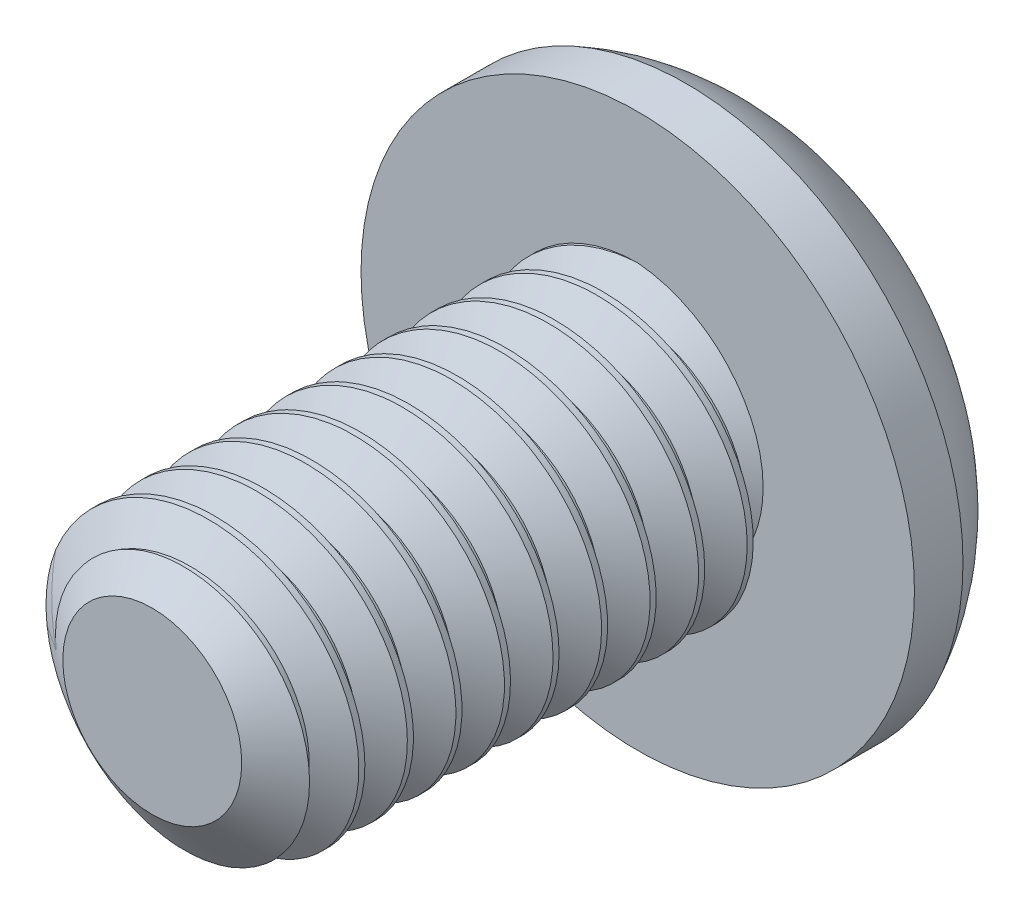
SolidWorks part; units mm, degrees
ref_plane "Front Plane" through (0, 0, 0) normal (0, 0, 1) x (1, 0, 0)
ref_plane "Top Plane" through (0, 0, 0) normal (0, 1, 0) x (1, 0, 0)
ref_plane "Right Plane" through (0, 0, 0) normal (1, 0, 0) x (0, 0, -1)
sketch "Sketch1" plane through (0, 0, 0) normal (0, 0, 1) x (1, 0, 0)
  circle A0 centre (0, 0) radius 1.5
  dimension "OD" = 3
extrude "Extrude1" add sketch "Sketch1" against normal blind 5
sketch "Sketch2" plane through (0, 0, 0) normal (0, 0, 1) x (1, 0, 0)
  circle A0 centre (0, 0) radius 1.5 construction
  circle A1 centre (0, 0) radius 1.5
curve "Helix/Spiral1" pitch 0.5 height 5.5 radius 1.5 centre (0, 0, 0) axis (0, 0, -1) start towards (0, 1, 0) parameters "pitch"=0.5
sketch "Sketch3" plane through (0, 0, 0) normal (1, 0, 0) x (0, 0, -1)
  line L0 (-0.4375, 1.5) -> (-0.25, 1.1752)
  line L1 (-0.25, 1.1752) -> (-0.1875, 1.1752)
  line L2 (-0.1875, 1.1752) -> (0, 1.5)
  line L3 (-0.4375, 1.5) -> (0, 1.5)
  line L4 (-0.2187, 1.5) -> (-0.2187, 1.1752) construction
  line L5 (-0.3437, 1.3376) -> (-0.0937, 1.3376) construction
  line L6 (0, 1.5) -> (0, -1.5) construction
  dimension "D1" = 0.0625
  dimension "D2" = 0.25
  dimension "D3" = 60
sweep "Cut-Sweep1" cut profiles "Sketch3" path "Helix/Spiral1"
sketch "Sketch4" plane through (0, 0, 0) normal (1, 0, 0) x (0, 0, -1)
  line L0 (0.4053, 1.5) -> (0, 0.9212)
  line L1 (0, 0.9212) -> (0, 1.5)
  line L2 (0.4053, 1.5) -> (0, 1.5)
  line L3 (-0.4375, 1.5) -> (0, 1.5) construction
  line L4 (0, 0) -> (7.0209, 0) construction
  dimension "D1" = 55
  dimension "D2" = 0.254
revolve "Cut-Revolve1" cut sketch "Sketch4" angle 360 about L4
sketch "Sketch5" plane through (0, 0, 0) normal (1, 0, 0) x (0, 0, -1)
  line L0 (5, -1.1822) -> (5, 1.0703) construction
  line L1 (5, 1.627) -> (28.1202, 1.627)
  line L2 (5, 1.627) -> (5, 0)
  line L3 (5, 0) -> (28, 0)
  line L4 (28, 1.2968) -> (28, 0)
  line L5 (28.1202, 1.627) -> (28, 1.2968)
  line L6 (0, 0) -> (9.9695, 0) construction
  point P3 (28, 1.627)
  point P10 (28, 1.627)
  dimension "D1" = 0.3302
  dimension "Thread min" = 28
  dimension "D2" = 0.127
  dimension "D3" = 20
revolve "partially thread" [suppressed] add sketch "Sketch5" angle 360 about L6
sketch "Sketch6" plane through (0, 0, -5) normal (0, 0, -1) x (-1, 0, 0)
  circle A0 centre (0, 0) radius 2.85
  dimension "head dia" = 5.7
extrude "Extrude2" add sketch "Sketch6" along normal blind 1.65
sketch "Sketch10" plane through (0, 0, 0) normal (1, 0, 0) x (0, 0, -1)
  line L0 (6.65, -2.85) -> (6.65, 2.85) construction
  line L1 (0, 0) -> (15.9584, 0) construction
  line L2 (6.65, 2.85) -> (5, 2.85) construction
  line L3 (5, 2.85) -> (5, -2.85) construction
  line L4 (5.5, 2.85) -> (5.5, 3.35)
  line L5 (5.5, 3.35) -> (7.15, 3.35)
  line L6 (7.15, 3.35) -> (7.15, 1)
  line L7 (6.65, 1) -> (7.15, 1)
  arc A0 (6.65, 1) -> (5.5, 2.85) centre (4.587, 1) ccw
  dimension "D1" = 2
  dimension "D2" = 0.5
  dimension "D3" = 0.5
revolve "Cut-Revolve2" cut sketch "Sketch10" angle 360 about L1
ref_plane "Plane1" through (0, 0, -6.65) normal (0, 0, 1) x (1, 0, 0)
sketch "Sketch7" plane through (0, 0, -6.65) normal (0, 0, -1) x (-1, 0, 0)
  line L1 (0, 1.1547) -> (-1, 0.5774)
  line L2 (-1, 0.5774) -> (-1, -0.5774)
  line L3 (-1, -0.5774) -> (0, -1.1547)
  line L4 (0, -1.1547) -> (1, -0.5774)
  line L5 (1, -0.5774) -> (1, 0.5774)
  line L6 (1, 0.5774) -> (0, 1.1547)
  circle A0 centre (0, 0) radius 1 construction
  dimension "hex dia" = 2
extrude "Cut-Extrude1" cut sketch "Sketch7" against normal blind 1.5
sketch "Sketch8" plane through (0, 0, -6.65) normal (0, 0, 1) x (1, 0, 0)
  circle A0 centre (0, 0) radius 1.1547
extrude "Cut-Extrude2" cut sketch "Sketch8" along normal through all draft 45
sketch "Sketch9" plane through (0, 0, 0) normal (1, 0, 0) x (0, 0, -1)
  line L0 (0, 1.5) -> (0, -1.5) construction
  line L1 (2.75, 1.5) -> (2.75, -1.5) construction
  dimension "D1" = 2.75
  dimension "D4" = 0.635
  dimension "D5" = 0.3302
equation "\"D3@Helix/Spiral1\" = \"screw length@Extrude1\"+\"pitch@Helix/Spiral1\""
equation "\"D1@Sketch3\" = \"pitch@Helix/Spiral1\"*.125"
equation "\"D2@Sketch3\" = \"pitch@Helix/Spiral1\"*.5"
equation "\"D1@Cut-Extrude1\" = \"hex dia@Sketch7\"*.75"
equation "\"D1@Sketch9\" = \"pitch@Helix/Spiral1\"*5.5"
equation "\"D1@Sketch10\" = \"hex dia@Sketch7\""
equation "\"D1@Plane1\" = \"head depth@Extrude2\""
